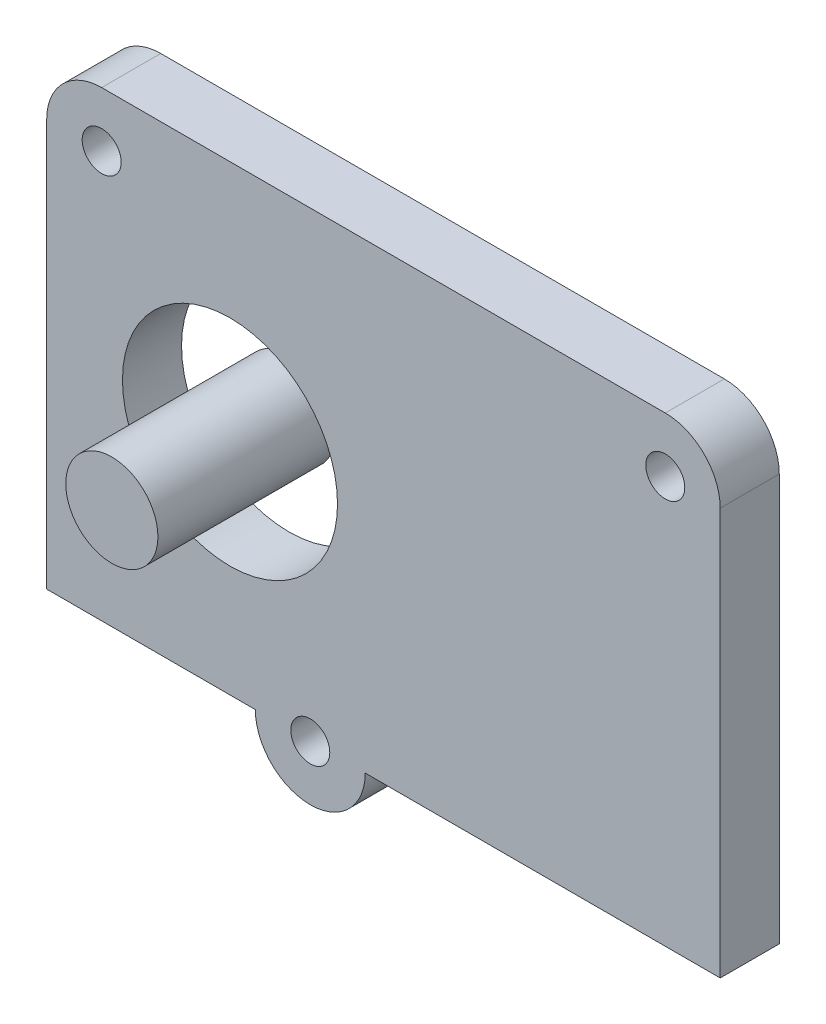
SolidWorks part; units mm, degrees
ref_plane "Front Plane" through (0, 0, 0) normal (0, 0, 1) x (1, 0, 0)
ref_plane "Top Plane" through (0, 0, 0) normal (0, 1, 0) x (1, 0, 0)
ref_plane "Right Plane" through (0, 0, 0) normal (1, 0, 0) x (0, 0, -1)
sketch "Sketch2" plane through (0, 0, 0) normal (0, 0, 1) x (1, 0, 0)
  line L0 (-21.7857, 11.479) -> (25.9143, 11.479) construction
  line L1 (25.9143, 11.479) -> (-4.1286, -22.9581) construction
  line L2 (-4.1286, -22.9581) -> (-21.7857, 11.479) construction
  line L3 (-21.7857, 11.479) -> (10.8929, -5.7395) construction
  line L4 (25.9143, 11.479) -> (-12.9571, -5.7395) construction
  line L5 (-26.4357, 11.479) -> (-26.4357, -22.9581)
  line L6 (-21.7857, 16.129) -> (25.9143, 16.129)
  line L7 (30.5643, 11.479) -> (30.5643, 3.209)
  line L8 (-8.7786, -22.9581) -> (-26.4357, -22.9581)
  line L9 (30.5643, -22.9581) -> (0.5214, -22.9581)
  line L10 (30.5643, -22.9581) -> (30.5643, 3.209)
  circle A0 centre (-10.9242, -4.414) radius 9.1
  circle A1 centre (-21.7857, 11.479) radius 1.65
  circle A2 centre (25.9143, 11.479) radius 1.65
  circle A3 centre (-4.1286, -22.9581) radius 1.65
  arc A4 (-21.7857, 16.129) -> (-26.4357, 11.479) centre (-21.7857, 11.479) ccw
  arc A5 (30.5643, 11.479) -> (25.9143, 16.129) centre (25.9143, 11.479) ccw
  arc A6 (-8.7786, -22.9581) -> (0.5214, -22.9581) centre (-4.1286, -22.9581) ccw
  circle A8 centre (-10.9242, -4.414) radius 3.9
  circle A10 centre (-4.1286, -22.9581) radius 4.65 construction
  circle A11 centre (-21.7857, 11.479) radius 4.65 construction
  circle A12 centre (25.9143, 11.479) radius 4.65 construction
  point P8 (0, 0)
  point P19 (0.5214, -22.9581)
  point P25 (30.5643, 11.479)
  point P29 (-17.1357, 11.479)
  dimension "D1" = 18.2
  dimension "D2" = 3.3
  dimension "D7" = 19.75
  dimension "D9" = 7.8
  dimension "D3" = 47.7
  dimension "D4" = 45.7
  dimension "D5" = 38.7
  dimension "D6" = 19.25
  dimension "D8" = 3
extrude "Boss-Extrude2" add sketch "Sketch2" along normal blind 5 contours L8 A6 L9 L10 L7 A5 L6 A4 L5 A0 A1 A2 A3 region at (3.7023, -3.7857, 0)
extrude "Boss-Extrude3" add sketch "Sketch2<4>" along normal blind 15 separate body contours A8 region at (-10.9242, -4.414, 0)
sketch "Sketch2<4>" plane through (0, 0, 0) normal (0, 0, 1) x (1, 0, 0) same geometry as "Sketch2"
